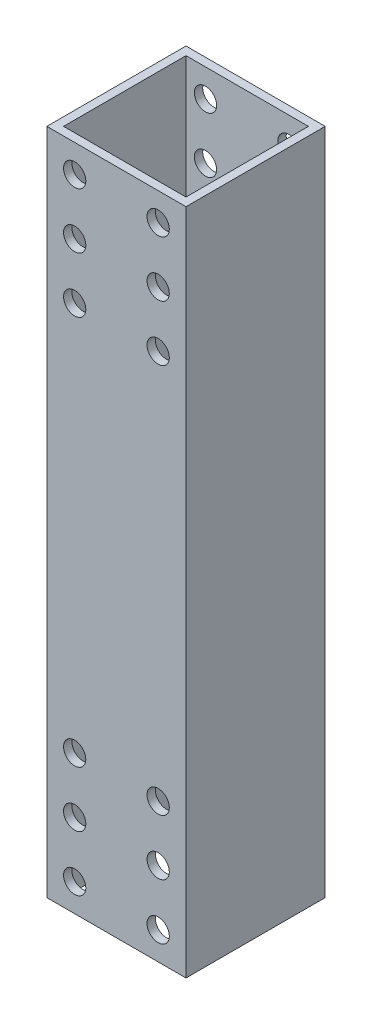
SolidWorks part; units mm, degrees
material "1060 Alloy"
ref_plane "Front Plane" through (0, 0, 0) normal (0, 0, 1) x (1, 0, 0)
ref_plane "Top Plane" through (0, 0, 0) normal (0, 1, 0) x (1, 0, 0)
ref_plane "Right Plane" through (0, 0, 0) normal (1, 0, 0) x (0, 0, -1)
sketch "Sketch1" plane through (0, 0, 0) normal (0, 1, 0) x (1, 0, 0)
  line L0 (0, 63.6278) -> (0, -69.3975) construction
  line L1 (-105.4586, 0) -> (105.4586, 0) construction
  line L2 (-11, 11) -> (-11, -11)
  line L3 (-12.5, 12.5) -> (12.5, 12.5)
  line L4 (-12.5, 12.5) -> (-12.5, -12.5)
  line L5 (-12.5, -12.5) -> (12.5, -12.5)
  line L6 (12.5, 12.5) -> (12.5, -12.5)
  line L7 (-11, -11) -> (11, -11)
  line L8 (11, 11) -> (11, -11)
  line L13 (-11, 11) -> (11, 11)
  point P5 (0, 0)
  dimension "D1" = 25
  dimension "D2" = 25
  dimension "D3" = 0
  dimension "D4" = 1.5
  dimension "D5" = 11
  dimension "D6" = 11
extrude "Boss-Extrude1" add sketch "Sketch1" along normal blind 60 and the other way blind 60
sketch "Sketch2" plane through (0, 0, -12.5) normal (0, 0, -1) x (-1, 0, 0)
  line L0 (0, 86.3155) -> (0, -83.2573) construction
  line L1 (-12.5, 60) -> (12.5, 60) construction
  circle A0 centre (7.5, 55) radius 2
  circle A1 centre (7.5, 45) radius 2
  circle A3 centre (-7.5, 55) radius 2
  circle A4 centre (-7.5, 45) radius 2
  circle A5 centre (7.5, 35) radius 2
  circle A6 centre (-7.5, 35) radius 2
  dimension "D1" = 7.5
  dimension "D5" = 10
  dimension "D2" = 7.5
  dimension "D3" = 7.5
  dimension "D4" = 7.5
  dimension "D6" = 10
  dimension "D7" = 5
  dimension "D8" = 10
  dimension "D9" = 7.5
  dimension "D10" = 5
  dimension "D11" = 10
  dimension "D12" = 7.5
extrude "Cut-Extrude1" cut sketch "Sketch2" against normal blind 25
mirror "Mirror1" about plane through (0, 0, 0) normal (0, 1, 0) of "Cut-Extrude1"
